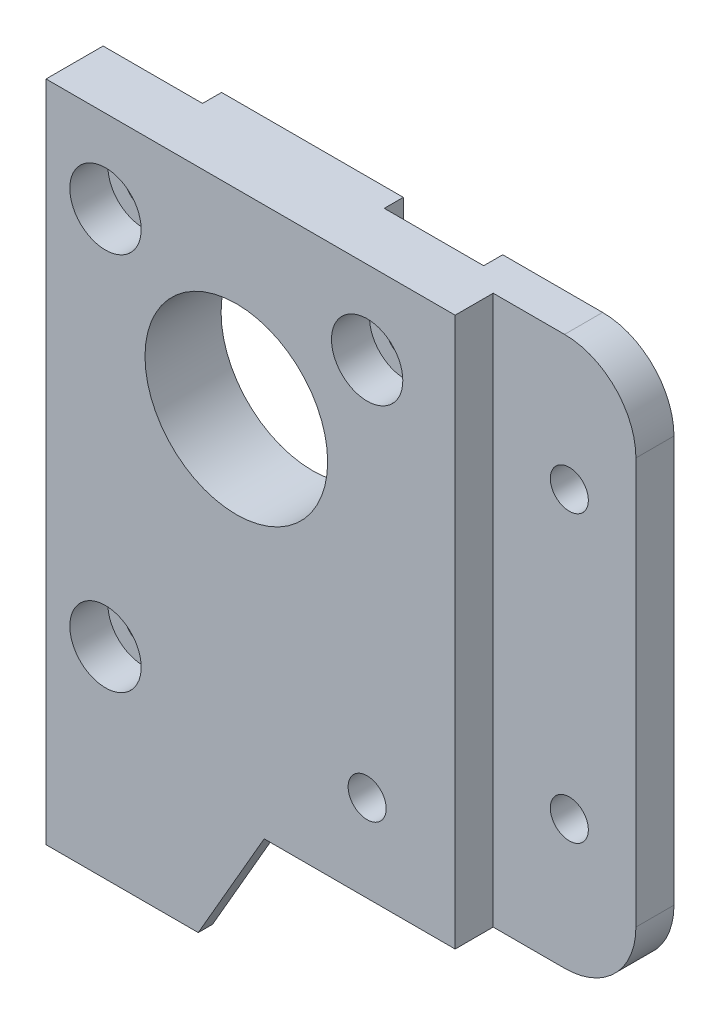
SolidWorks part; units mm, degrees
material "Custom Plastic"
ref_plane "Front Plane" through (0, 0, 0) normal (0, 0, 1) x (1, 0, 0)
ref_plane "Top Plane" through (0, 0, 0) normal (0, 1, 0) x (1, 0, 0)
ref_plane "Right Plane" through (0, 0, 0) normal (1, 0, 0) x (0, 0, -1)
sketch "Sketch1" plane through (0, 0, 0) normal (0, 0, 1) x (1, 0, 0)
  line L0 (-13.75, -19.7) -> (-9.788, -16.65) construction
  line L3 (20, 28.85) -> (38, 28.85)
  line L8 (20, -28.85) -> (-20, -28.85)
  line L9 (20, -28.85) -> (20, 28.85) construction
  line L10 (38, 28.85) -> (38, -28.85)
  line L11 (20, 28.85) -> (-20, 28.85)
  line L14 (-20, -28.85) -> (-20, 28.85)
  line L15 (20, -28.85) -> (-20, 28.85) construction
  line L16 (20, 28.85) -> (-20, -28.85) construction
  line L17 (-16.312, -16.3719) -> (-12.35, -13.3219)
  line L18 (-11.188, -23.0281) -> (-7.226, -19.9781)
  line L19 (0, -28.85) -> (0, 28.85) construction
  line L22 (38, -28.85) -> (20, -28.85)
  line L23 (17.2017, -17.3071) -> (20, -21.3437)
  line L24 (9.55, -19.7) -> (9.55, -28.85)
  line L25 (-9.55, 20.15) -> (-9.55, 28.85)
  line L26 (-17.2017, 17.7571) -> (-20, 21.7937)
  line L27 (9.55, 20.15) -> (9.55, 28.85)
  line L28 (17.2017, 17.7571) -> (20, 21.7937)
  line L29 (20, 21.7937) -> (20, 28.85)
  line L30 (-16.312, -16.3719) -> (-20, -16.3719)
  line L31 (20, -28.85) -> (20, -21.3437)
  line L33 (-13.75, -23.9) -> (-13.75, -28.85)
  circle A18 centre (-13.75, 20.15) radius 4.2
  circle A19 centre (13.75, 20.15) radius 4.2
  circle A20 centre (13.75, -19.7) radius 4.2
  arc A21 (-16.312, -16.3719) -> (-11.188, -23.0281) centre (-13.75, -19.7) ccw
  arc A22 (-7.226, -19.9781) -> (-12.35, -13.3219) centre (-9.788, -16.65) ccw
  circle A23 centre (0, 8.8) radius 9.6
  circle A24 centre (-5.725, -6.1) radius 4.2
  circle A25 centre (5.725, -6.1) radius 4.2
  point P0 (0, 0)
  point P14 (-6.4599, -14.088)
  point P31 (-11.769, -18.175)
  point P37 (5.725, -10.3)
  point P43 (20, 28.85)
  point P46 (-20, 28.85)
  dimension "D1" = 57.7
  dimension "D2" = 40
  dimension "D3" = 12.2
  dimension "D4" = 8.4
  dimension "D5" = 8.4
  dimension "D6" = 19.2
  dimension "D7" = 9.15
  dimension "D8" = 27.5
  dimension "D9" = 39.85
  dimension "D10" = 5
  dimension "D12" = 20.05
  dimension "D13" = 11.45
  dimension "D14" = 22.75
  dimension "D15" = 18
extrude "Boss-Extrude1" add sketch "Sketch1" along normal blind 2 contours L11 L14 L8 L9 A25 A24 A23 A22 L18 A21 L17 A20 A19 A18 region at (12.4683, -0.6196, 0)
sketch "Sketch4" plane through (0, 0, 2) normal (0, 0, 1) x (1, 0, 0)
  line L0 (0, -28.85) -> (0, 29) construction
  line L6 (38, -28.85) -> (20, -28.85) construction
  line L8 (-20, -28.85) -> (38, -28.85)
  line L11 (38, -28.85) -> (38, 28.85)
  line L12 (-20, 28.85) -> (-20, -28.85)
  line L13 (-20, -16.3719) -> (-20, 21.7937) construction
  line L14 (-20, 28.85) -> (38, 28.85)
  line L15 (20, 28.85) -> (38, 28.85) construction
  line L16 (38, 28.85) -> (38, -28.85) construction
  circle A2 centre (13.75, -19.7) radius 2
  circle A3 centre (-13.75, 20.15) radius 2
  circle A4 centre (13.75, 20.15) radius 2
  circle A10 centre (-13.75, -19.7) radius 2
  circle A11 centre (0, 8.8) radius 9.6
  circle A12 centre (0, 8.8) radius 9.6 construction
  dimension "D1" = 4
extrude "Boss-Extrude3" add sketch "Sketch4" along normal blind 2
sketch "Sketch5" plane through (0, 0, 4) normal (0, 0, 1) x (1, 0, 0)
  line L0 (-20, 0) -> (38, 0) construction
  line L3 (-20, 28.85) -> (-20, -28.85) construction
  line L4 (38, -28.85) -> (38, 28.85) construction
  circle A0 centre (31, 15) radius 2
  circle A1 centre (31, -15) radius 2
  dimension "D1" = 4
  dimension "D2" = 15
  dimension "D3" = 51
extrude "Cut-Extrude1" cut sketch "Sketch5" against normal blind 4
ref_plane "Plane1" through (0, 0, 0) normal (0, 0, -1) x (-1, 0, 0)
sketch "Sketch6" plane through (0, 0, 4) normal (0, 0, 1) x (1, 0, 0)
  line L0 (23, 28.85) -> (23, -28.85)
  line L1 (38, 28.85) -> (-20, 28.85) construction
  line L2 (-20, -28.85) -> (38, -28.85) construction
  line L3 (38, -28.85) -> (38, 28.85) construction
  circle A52 centre (-13.75, 20.15) radius 3.75
  circle A53 centre (13.75, 20.15) radius 3.75
  circle A54 centre (31, 15) radius 2
  circle A55 centre (13.75, -19.7) radius 3.75
  circle A56 centre (-13.75, -19.7) radius 3.75
  circle A57 centre (31, -15) radius 2
  circle A59 centre (31, 15) radius 2 construction
  circle A60 centre (31, -15) radius 2 construction
  line M5 (-20, 28.85) -> (-20, -28.85)
  line M6 (-20, -28.85) -> (38, -28.85)
  line M7 (38, -28.85) -> (38, 28.85)
  line M8 (38, 28.85) -> (-20, 28.85)
  circle M9 centre (13.75, -19.7) radius 2
  circle M11 centre (0, 8.8) radius 9.6
  dimension "D1" = 7.5
  dimension "D2" = 15
extrude "Boss-Extrude4" add sketch "Sketch6" along normal blind 4 contours A57 A56 A55 A54 A53 A52 M8 M5 M6 M7 M11 | A55 M9 region at (1.8471, -1.2843, 4) region at (10.1061, -19.7, 4)
sketch "Sketch7" plane through (0, 0, 4) normal (0, 0, 1) x (1, 0, 0)
  line L0 (38, -28.85) -> (38, 28.85) construction
  line L1 (30.5, 28.85) -> (38, 28.85)
  line L2 (38, 28.85) -> (38, 21.35)
  line L3 (-20, 0) -> (38, 0) construction
  line L4 (-20, 28.85) -> (-20, -28.85) construction
  line L5 (38, -28.85) -> (38, -21.35)
  line L6 (30.5, -28.85) -> (38, -28.85)
  arc A0 (38, 21.35) -> (30.5, 28.85) centre (30.5, 21.35) ccw
  arc A1 (38, -21.35) -> (30.5, -28.85) centre (30.5, -21.35) cw
  dimension "D1" = 15
extrude "Cut-Extrude2" cut sketch "Sketch7" against normal through all
sketch "Sketch9" plane through (-20, 0, 0) normal (-1, 0, 0) x (0, 0, 1)
  line L0 (8, -28.85) -> (8, -40.85)
  line L2 (8, -40.85) -> (0, -40.85)
  line L3 (0, -40.85) -> (0, -35.15)
  line L4 (0, -35.15) -> (2, -35.15)
  line L5 (2, -35.15) -> (2, -28.85)
  line L6 (8, -28.85) -> (2, -28.85) construction
  line L7 (0, -16.3719) -> (0, 21.7937) construction
  line L9 (2, -28.85) -> (8, -28.85)
  dimension "D1" = 6
  dimension "D2" = 12
  dimension "D3" = 6.3
extrude "Boss-Extrude5" add sketch "Sketch9" against normal blind 6
sketch "Sketch10" plane through (0, 0, 8) normal (0, 0, 1) x (1, 0, 0)
  line L0 (-14, -40.85) -> (-4, -40.85)
  line L1 (-4, -40.85) -> (2.9282, -28.85)
  line L3 (2.9282, -28.85) -> (-14, -28.85)
  line L4 (-14, -28.85) -> (-14, -40.85)
  dimension "D1" = 10
  dimension "D2" = 120
extrude "Boss-Extrude6" add sketch "Sketch10" against normal blind 1.5
